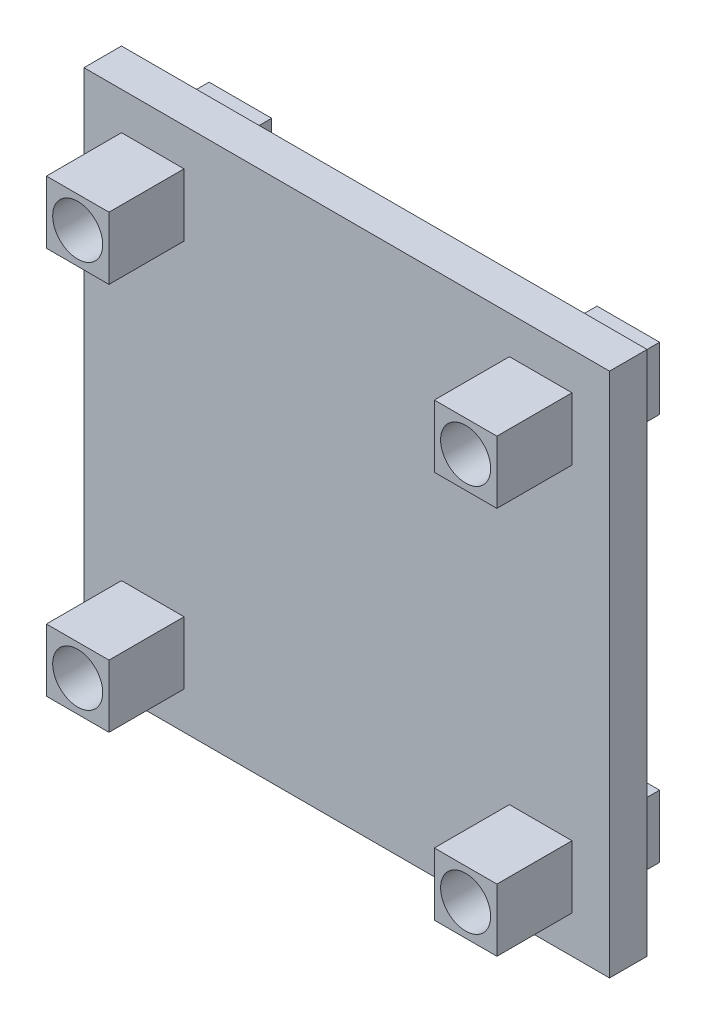
SolidWorks part; units mm, degrees
ref_plane "Front Plane" through (0, 0, 0) normal (0, 0, 1) x (1, 0, 0)
ref_plane "Top Plane" through (0, 0, 0) normal (0, 1, 0) x (1, 0, 0)
ref_plane "Right Plane" through (0, 0, 0) normal (1, 0, 0) x (0, 0, -1)
sketch "Sketch2" plane through (0, 0, 0) normal (0, 0, 1) x (1, 0, 0)
  line L0 (0, -55) -> (0, 55) construction
  line L1 (-21, -21) -> (21, -21)
  line L2 (-21, -21) -> (-21, 21)
  line L3 (-21, 21) -> (21, 21)
  line L4 (21, -21) -> (21, 21)
  line L5 (-21, -21) -> (21, 21) construction
  line L6 (-21, 21) -> (21, -21) construction
  line L7 (-20, -20) -> (20, -20)
  line L8 (-20, -20) -> (-20, 20)
  line L9 (-20, 20) -> (20, 20)
  line L10 (20, -20) -> (20, 20)
  line L11 (-20, -20) -> (20, 20) construction
  line L12 (-20, 20) -> (20, -20) construction
  line L13 (-15.5, -15.5) -> (15.5, -15.5) construction
  line L14 (-15.5, -15.5) -> (-15.5, 15.5) construction
  line L15 (-15.5, 15.5) -> (15.5, 15.5) construction
  line L16 (15.5, -15.5) -> (15.5, 15.5) construction
  line L17 (-15.5, -15.5) -> (15.5, 15.5) construction
  line L18 (-15.5, 15.5) -> (15.5, -15.5) construction
  line L19 (-18, 13) -> (-13, 13)
  line L20 (-18, 13) -> (-18, 18)
  line L21 (-18, 18) -> (-13, 18)
  line L22 (-13, 13) -> (-13, 18)
  line L23 (-18, 13) -> (-13, 18) construction
  line L24 (-18, 18) -> (-13, 13) construction
  line L25 (18, 13) -> (18, 18)
  line L26 (18, 13) -> (13, 13)
  line L27 (13, 13) -> (13, 18)
  line L28 (18, 18) -> (13, 18)
  line L29 (55, 0) -> (-55, 0) construction
  line L30 (18, -13) -> (13, -13)
  line L31 (18, -13) -> (18, -18)
  line L32 (18, -18) -> (13, -18)
  line L33 (13, -13) -> (13, -18)
  line L34 (-18, -13) -> (-18, -18)
  line L35 (-18, -13) -> (-13, -13)
  line L36 (-13, -13) -> (-13, -18)
  line L37 (-18, -18) -> (-13, -18)
  circle A0 centre (-15.5, 15.5) radius 2
  circle A1 centre (15.5, 15.5) radius 2
  circle A2 centre (15.5, -15.5) radius 2
  circle A3 centre (-15.5, -15.5) radius 2
  point P0 (0, 0)
  point P6 (0, 0)
  point P23 (0, 0)
  dimension "D1" = 42
  dimension "D2" = 42
  dimension "D3" = 40
  dimension "D4" = 5
  dimension "D5" = 5
extrude "Boss-Extrude1" add sketch "Sketch2" along normal blind 3 contours L3 L4 L1 L2
extrude "Boss-Extrude9" add sketch "Sketch2<5>" along normal blind 6 from surface contours L34 L37 L36 L35 A3 | L30 L33 L32 L31 A2 | L25 L28 L27 L26 A1 | L19 L22 L21 L20 A0 | L36 L37 L34 L35 | L30 L33 L32 L31 | L25 L28 L27 L26 | L22 L21 L20 L19 region at (-17.9293, 15.5, 0) region at (15.5, 13.0707, 0) region at (17.9293, -15.5, 0) region at (-15.5, -13.0707, 0) starting at face at (0, 0, 3)
sketch "Sketch2<5>" plane through (0, 0, 0) normal (0, 0, 1) x (1, 0, 0) same geometry as "Sketch2"
extrude "Cut-Extrude3" cut sketch "Sketch2<7>" along normal through all both and the other way through all contours A0 | A1 | A2 | A3
sketch "Sketch2<7>" plane through (0, 0, 0) normal (0, 0, 1) x (1, 0, 0) same geometry as "Sketch2"
extrude "Boss-Extrude10" add sketch "Sketch2<6>" against normal blind 4 from surface contours L34 L37 L36 L35 A3 | L30 L33 L32 L31 A2 | L25 L28 L27 L26 A1 | L19 L22 L21 L20 A0 region at (-17.9293, 15.5, 0) region at (15.5, 13.0707, 0) region at (17.9293, -15.5, 0) region at (-15.5, -13.0707, 0) starting at face at (-17.5, -15.5, 0)
sketch "Sketch2<6>" plane through (0, 0, 0) normal (0, 0, 1) x (1, 0, 0) same geometry as "Sketch2"
